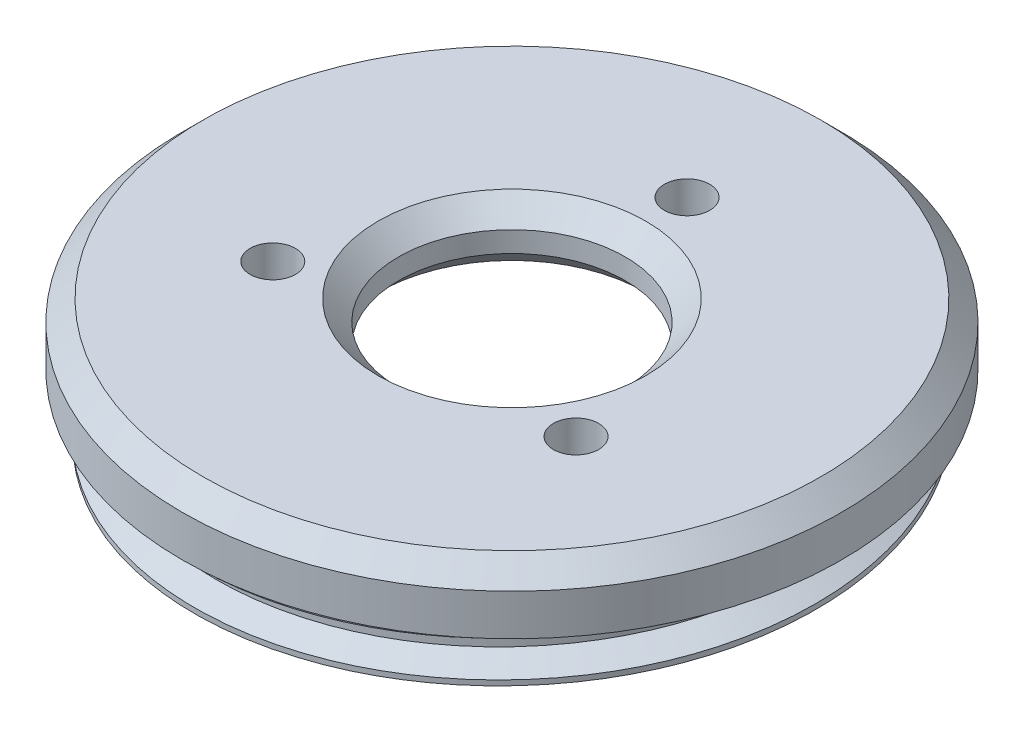
SolidWorks part; units mm, degrees
ref_plane "Спереди" through (0, 0, 0) normal (0, 0, 1) x (1, 0, 0)
ref_plane "Сверху" through (0, 0, 0) normal (0, 1, 0) x (1, 0, 0)
ref_plane "Справа" through (0, 0, 0) normal (1, 0, 0) x (0, 0, -1)
sketch "Эскиз1" plane through (0, 0, 0) normal (0, 1, 0) x (1, 0, 0)
  circle A0 centre (0, 0) radius 16
  circle A1 centre (0, 0) radius 8.5 construction
  circle A2 centre (0, 8.5) radius 1.1
  circle A3 centre (7.3612, -4.25) radius 1.1
  circle A4 centre (-7.3612, -4.25) radius 1.1
  circle A5 centre (0, 0) radius 5.5
  dimension "D1" = 32
  dimension "D2" = 17
  dimension "D3" = 2.2
  dimension "D5" = 11
  dimension "D4" = 3
extrude "Бобышка-Вытянуть1" add sketch "Эскиз1" along normal blind 3
sketch "Эскиз2" plane through (0, 0, 0) normal (0, -1, 0) x (1, 0, 0)
  circle A0 centre (0, 0) radius 13
  circle A1 centre (0, 0) radius 14
  dimension "D1" = 26
extrude "Бобышка-Вытянуть2" add sketch "Эскиз2" along normal blind 3
thread "Резьба1" pitch 2 method extrude trim with start face yes profile "Профиль резьбы1" start angle 0, offset 2, length 0, pitch 2, diameter 28
ref_plane "Плоскость1" through (14, -5, 0) normal (0, 0, 1) x (1, 0, 0)
sketch "Профиль резьбы1" plane through (14, -5, 0) normal (0, 0, 1) x (1, 0, 0)
  line L0 (0, 0) -> (0, 2) construction
  line L1 (0, 0) -> (1.0825, 0.625)
  line L2 (1.0825, 0.625) -> (1.0825, 0.875)
  line L3 (1.0825, 0.875) -> (0, 1.5)
  line L4 (1.0825, 0.75) -> (0, 0.75) construction
  line L11 (0, 0) -> (0, 1.5)
  point P2 (0, 0)
  dimension "Pitch" = 2
  dimension "Profile_Angle" = 60
  dimension "Profile_Land" = 0.25
  dimension "Profile_Height" = 1.0825
chamfer "Фаска1" distance 1 angle 45 5 edges at (0, 3, 16) (7.3612, 0, 5.35) (0, 0, -7.4) (-7.3612, 0, 5.35) (0, 3, 5.5)
chamfer "Фаска2" distance 1 angle 45 1 edges at (0, 0, 5.5)
equation "\"bearing_d1\"= 6'Bearing inner diameter"
equation "\"bearing_d2\"= 17'Bearing external diameter"
equation "\"bearing h\"= 6'Bearing heigh"
equation "\"pin_d\"= 2'Pin diameter"
equation "\"pin_h\"= 12'Pin heigh"
equation "\"print_offset\"= 0.2'Offset for printing holes"
equation "\"module_diameter\"= 41"
equation "\"D2@Эскиз1\"=8.5*2"
equation "\"D3@Эскиз1\"=\"print_offset\"+2"
equation "\"motor_diameter\"= 32"
equation "\"D1@Эскиз1\"=\"motor_diameter\""
equation "\"D1@Эскиз2\"=\"motor_diameter\"-6"
